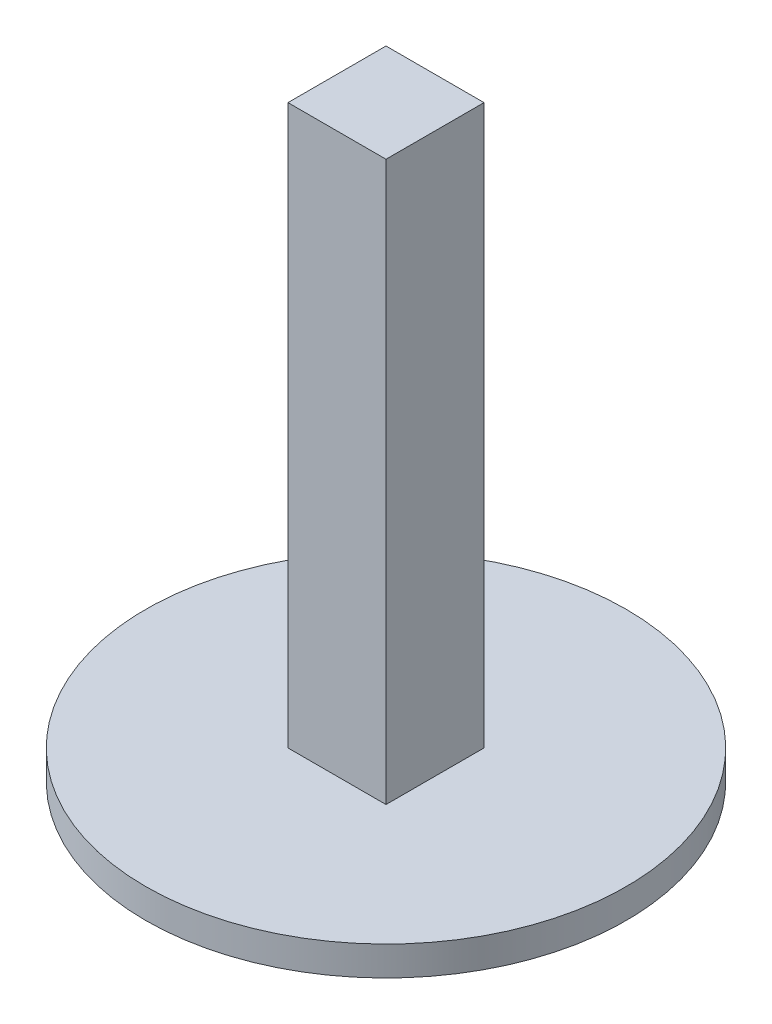
SolidWorks part; units mm, degrees
ref_plane "Front Plane" through (0, 0, 0) normal (0, 0, 1) x (1, 0, 0)
ref_plane "Top Plane" through (0, 0, 0) normal (0, 1, 0) x (1, 0, 0)
ref_plane "Right Plane" through (0, 0, 0) normal (1, 0, 0) x (0, 0, -1)
sketch "Sketch1" plane through (0, 0, 0) normal (0, 1, 0) x (1, 0, 0)
  line L1 (-1.25, -1.25) -> (1.25, -1.25)
  line L2 (-1.25, -1.25) -> (-1.25, 1.25)
  line L3 (-1.25, 1.25) -> (1.25, 1.25)
  line L4 (1.25, -1.25) -> (1.25, 1.25)
  line L5 (-1.25, -1.25) -> (1.25, 1.25) construction
  line L6 (-1.25, 1.25) -> (1.25, -1.25) construction
  circle A0 centre (0, 0) radius 6.125
  dimension "D1" = 12.25
  dimension "D2" = 2.5
  dimension "D3" = 2.5
extrude "Boss-Extrude1" add sketch "Sketch1" along normal blind 0.75
extrude "Boss-Extrude2" add sketch "Sketch1<2>" along normal blind 15 contours L2 L3 L4 L1
sketch "Sketch1<2>" plane through (0, 0, 0) normal (0, 1, 0) x (1, 0, 0) same geometry as "Sketch1"
